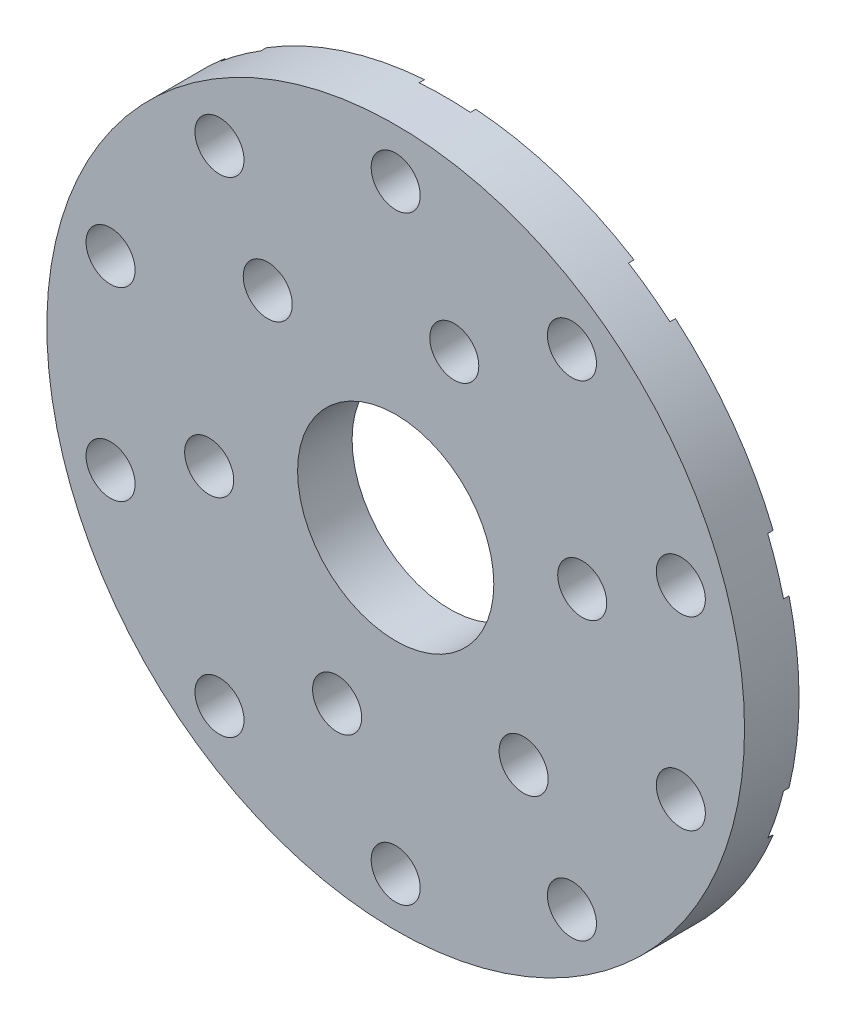
SolidWorks part; units mm, degrees
ref_plane "前视基准面" through (0, 0, 0) normal (0, 0, 1) x (1, 0, 0)
ref_plane "上视基准面" through (0, 0, 0) normal (0, 1, 0) x (1, 0, 0)
ref_plane "右视基准面" through (0, 0, 0) normal (1, 0, 0) x (0, 0, -1)
sketch "草图1" plane through (0, 0, 0) normal (0, 0, 1) x (1, 0, 0)
  circle A0 centre (0, 0) radius 32
  dimension "D1" = 64
extrude "凸台-拉伸1" add sketch "草图1" along normal blind 5
sketch "草图3" plane through (0, 0, 0) normal (0, 0, -1) x (-1, 0, 0)
  circle A0 centre (0, 0) radius 9
  dimension "D1" = 18
extrude "切除-拉伸1" cut sketch "草图3" against normal up to next
hole_wizard "打孔尺寸(%根据六角头螺)栓 全螺纹的类型1" positions "草图7" profile "草图5" counterbore size "M4" standard "GB"
sketch "草图7" plane through (0, 0, 0) normal (0, 0, -1) x (-1, 0, 0)
  line L0 (0, 0) -> (0, 33.5232) construction
  circle A0 centre (0, 0) radius 27.5 construction
  point P0 (0, 27.5)
  dimension "D1" = 55
sketch "草图5" plane through (0, 27.5, 0) normal (1, 0, 0) x (0, 1, 0)
  line L0 (0, 0) -> (0, 8.3519)
  line L1 (0, 8.3519) -> (2.25, 7)
  line L2 (2.25, 7) -> (2.25, 0.5)
  line L3 (2.25, 0.5) -> (5, 0.5)
  line L4 (5, 0.5) -> (5, 0)
  line L5 (5, 0) -> (0, 0)
  line L10 (0, 8.3519) -> (-2.25, 7) construction
  line L11 (0, -6.35) -> (0, 107.95) construction
  dimension "孔直径" = 4.5
  dimension "孔深度" = 7
  dimension "柱形沉头孔直径" = 10
  dimension "柱形沉头孔深度" = 0.5
  dimension "导头角度" = 118
ref_axis "基准轴1" through (0, 0, 5) along (0, 0, -1)
pattern_circular "阵列(圆周)1" count 10 over 360 about axis through (0, 0, 5) along (0, 0, -1) of "打孔尺寸(%根据六角头螺)栓 全螺纹的类型1"
hole_wizard "打孔尺寸(%根据六角头螺)栓 全螺纹的类型2" positions "草图11" profile "草图10" counterbore size "M4" standard "GB"
sketch "草图11" plane through (0, 0, 0) normal (0, 0, -1) x (-1, 0, 0)
  line L1 (0, 0) -> (0, 35.8193) construction
  line L3 (0, 0) -> (-11.3182, 34.8338) construction
  circle A0 centre (0, 0) radius 17.5 construction
  point P0 (-5.3724, 16.655)
  dimension "D1" = 35
  dimension "D2" = 18
sketch "草图10" plane through (5.3724, 16.655, 0) normal (1, 0, 0) x (0, 1, 0)
  line L0 (0, 0) -> (0, 7.9519)
  line L1 (0, 7.9519) -> (2.25, 6.6)
  line L2 (2.25, 6.6) -> (2.25, 0.5)
  line L3 (2.25, 0.5) -> (5, 0.5)
  line L4 (5, 0.5) -> (5, 0)
  line L5 (5, 0) -> (0, 0)
  line L10 (0, 7.9519) -> (-2.25, 6.6) construction
  line L11 (0, -6.35) -> (0, 107.95) construction
  dimension "孔直径" = 4.5
  dimension "孔深度" = 6.6
  dimension "柱形沉头孔直径" = 10
  dimension "柱形沉头孔深度" = 0.5
  dimension "导头角度" = 118
pattern_circular "阵列(圆周)2" count 6 over 360 about axis through (0, 0, 5) along (0, 0, -1) of "打孔尺寸(%根据六角头螺)栓 全螺纹的类型2"
